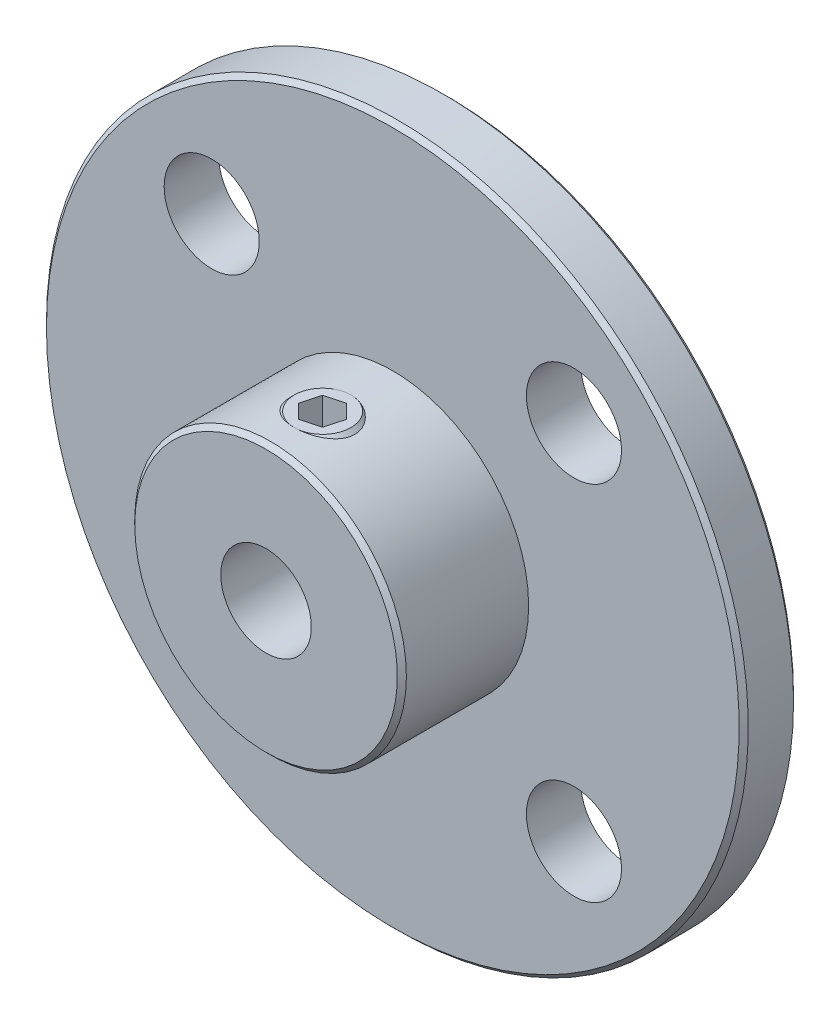
SolidWorks part; units mm, degrees
material "1060 Alloy"
material "Plain Carbon Steel"
material "1060 Alloy"
ref_plane "Front Plane" through (0, 0, 0) normal (0, 0, 1) x (1, 0, 0)
ref_plane "Top Plane" through (0, 0, 0) normal (0, 1, 0) x (1, 0, 0)
ref_plane "Right Plane" through (0, 0, 0) normal (1, 0, 0) x (0, 0, -1)
ref_axis "Axis1" through (0, 0, -7.6563) along (0, 0, 1)
sketch "Sketch1" plane through (0, 0, 0) normal (0, 1, 0) x (1, 0, 0)
  line L0 (2, 0) -> (2, -8)
  line L1 (2, -8) -> (6, -8)
  line L2 (6, -8) -> (6, -2.4)
  line L3 (6, -2.4) -> (15.5, -2.4)
  line L4 (15.5, -2.4) -> (15.5, 0)
  line L5 (15.5, 0) -> (2, 0)
  line L7 (0, 122.4579) -> (0, -141.6286) construction
  line L8 (0, 88.99) -> (0, -88.99) construction
  dimension "D1" = 4
  dimension "D2" = 12
  dimension "D3" = 31
  dimension "D4" = 2.4
  dimension "D5" = 8
revolve "Revolve1" add sketch "Sketch1" angle 360 about L7
sketch "Sketch2" plane through (0, 0, 0) normal (0, 1, 0) x (1, 0, 0)
  line L0 (-6, -8) -> (6, -8) construction
  line L1 (0, 3.6487) -> (0, -20.516) construction
  circle A0 centre (0, -5.5) radius 1.25
  dimension "D1" = 2.5
  dimension "D2" = 2.5
extrude "Cut-Extrude1" cut sketch "Sketch2" along normal through all
sketch "Sketch3" plane through (0, 0, 0) normal (0, 0, -1) x (-1, 0, 0)
  line L0 (0, 17.861) -> (0, 0) construction
  line L1 (0, 0) -> (17.861, 17.861) construction
  circle A0 centre (0, 0) radius 11.3137 construction
  circle A1 centre (8, 8) radius 2.1
  dimension "D1" = 8
  dimension "D3" = 4.2
  dimension "D2" = 45
extrude "Cut-Extrude2" cut sketch "Sketch3" against normal through all
pattern_circular "CirPattern1" count 4 over 360 about axis through (0, 0, -7.6563) along (0, 0, 1) of "Cut-Extrude2"
chamfer "Chamfer1" distance 0.2 angle 45 3 edges at (-6, 0, 8) (-15.5, 0, 2.4) (-15.5, 0, 0)
ref_plane "Plane1" through (0, 1.5, 0) normal (0, 1, 0) x (1, 0, 0)
sketch "Sketch4" plane through (0, 1.5, 0) normal (0, 1, 0) x (1, 0, 0)
  circle A0 centre (0, -5.5) radius 1.5
  dimension "D1" = 3
extrude "Boss-Extrude1" add sketch "Sketch4" along normal blind 4.5 separate body
chamfer "Chamfer2" distance 0.25 angle 45 1 edges at (0, 6, 7)
sketch "Sketch5" plane through (0, 6, 0) normal (0, 1, 0) x (1, 0, 0)
  line L1 (0.837, -5.2778) -> (0.226, -4.664)
  line L2 (0.226, -4.664) -> (-0.611, -4.8862)
  line L3 (-0.611, -4.8862) -> (-0.837, -5.7222)
  line L4 (-0.837, -5.7222) -> (-0.226, -6.336)
  line L5 (-0.226, -6.336) -> (0.611, -6.1138)
  line L6 (0.611, -6.1138) -> (0.837, -5.2778)
  circle A0 centre (0, -5.5) radius 0.75 construction
  dimension "D1" = 1.5
extrude "Cut-Extrude3" cut sketch "Sketch5" against normal blind 2
